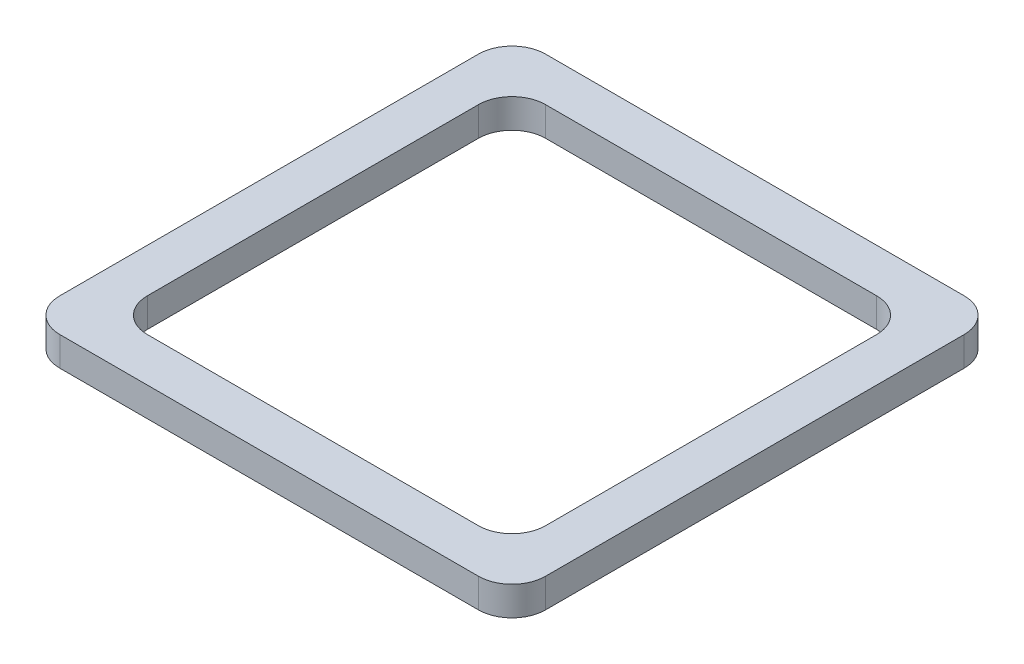
SolidWorks part; units mm, degrees
ref_plane "Front Plane" through (0, 0, 0) normal (0, 0, 1) x (1, 0, 0)
ref_plane "Top Plane" through (0, 0, 0) normal (0, 1, 0) x (1, 0, 0)
ref_plane "Right Plane" through (0, 0, 0) normal (1, 0, 0) x (0, 0, -1)
sketch "Sketch1" plane through (0, 0, 0) normal (0, 1, 0) x (1, 0, 0)
  line L0 (-6.825, -6.825) -> (-5.675, -6.825) construction
  line L1 (-8.325, -8.325) -> (8.325, -8.325)
  line L2 (-8.325, -8.325) -> (-8.325, 8.325)
  line L3 (-8.325, 8.325) -> (8.325, 8.325)
  line L4 (8.325, -8.325) -> (8.325, 8.325)
  line L5 (-8.325, -8.325) -> (8.325, 8.325) construction
  line L6 (-8.325, 8.325) -> (8.325, -8.325) construction
  line L7 (-6.825, -6.825) -> (6.825, -6.825)
  line L8 (-6.825, -6.825) -> (-6.825, 6.825)
  line L9 (-6.825, 6.825) -> (6.825, 6.825)
  line L10 (6.825, -6.825) -> (6.825, 6.825)
  line L11 (-6.825, -6.825) -> (6.825, 6.825) construction
  line L12 (-6.825, 6.825) -> (6.825, -6.825) construction
  line L13 (-6.825, -6.825) -> (-6.825, -5.675) construction
  arc A0 (-5.675, -6.825) -> (-6.825, -5.675) centre (-5.675, -5.675) cw
  arc A1 (-6.825, 5.675) -> (-5.675, 6.825) centre (-5.675, 5.675) cw
  arc A2 (5.675, 6.825) -> (6.825, 5.675) centre (5.675, 5.675) cw
  arc A3 (6.825, -5.675) -> (5.675, -6.825) centre (5.675, -5.675) cw
  point P0 (0, 0)
  point P6 (0, 0)
  point P26 (0, 0)
  dimension "D1" = 16.65
  dimension "D3" = 13.65
  dimension "D4" = 1.15
  dimension "D5" = 1.15
  dimension "D6" = 4
extrude "Boss-Extrude1" add sketch "Sketch1" along normal blind 1 contours L1 L4 L3 L2 L10 L7 L8 L9 | L7 A0 L8 | L8 A1 L9 | L9 A2 L10 | L10 A3 L7 region at (-8.0895, 0, 0) region at (-6.5681, 0, 6.5681) region at (6.5681, 0, 6.5681) region at (-6.5681, 0, -6.5681) region at (6.5681, 0, -6.5681)
ref_axis "Axis1" through (0, 0, 0) along (0, 1, 0)
fillet "Fillet1" radius 1.15 4 edges at (-8.325, 0.5, -8.325) (-8.325, 0.5, 8.325) (8.325, 0.5, 8.325) (8.325, 0.5, -8.325)
